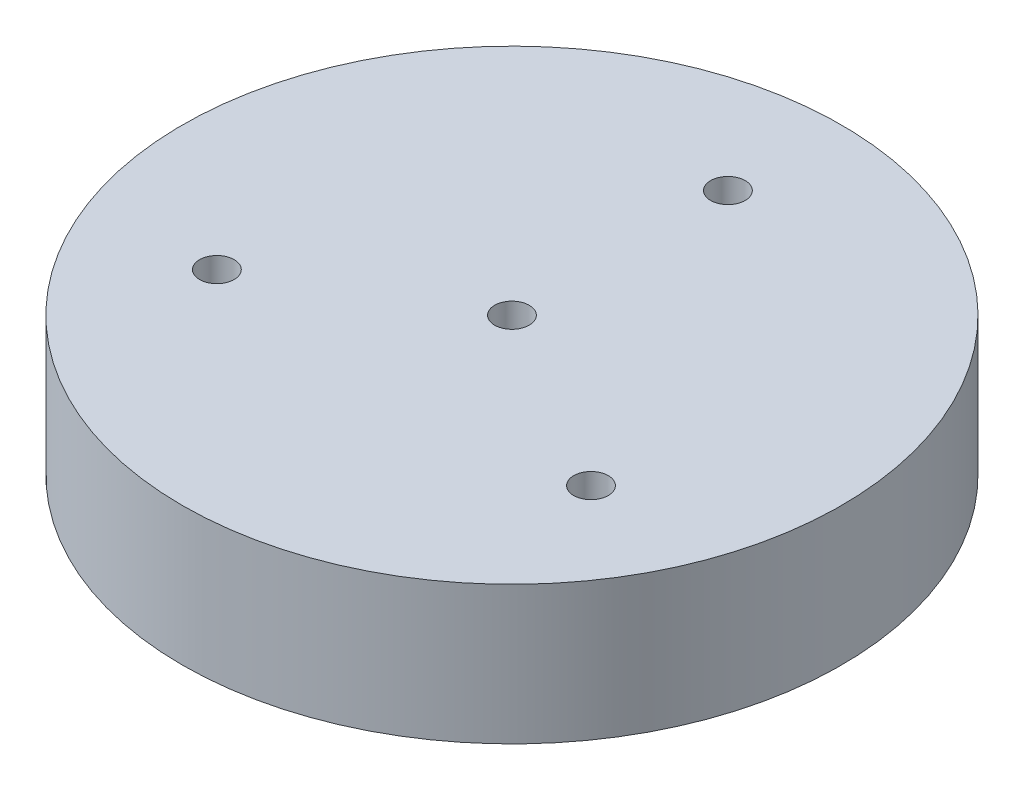
SolidWorks part; units mm, degrees
ref_plane "Ebene vorne" through (0, 0, 0) normal (0, 0, 1) x (1, 0, 0)
ref_plane "Ebene oben" through (0, 0, 0) normal (0, 1, 0) x (1, 0, 0)
ref_plane "Ebene rechts" through (0, 0, 0) normal (1, 0, 0) x (0, 0, -1)
sketch "Sketch1" plane through (0, 0, 0) normal (0, 1, 0) x (1, 0, 0)
  circle A0 centre (0, 0) radius 76.29
  dimension "D1" = 152.58
extrude "Boss-Extrude1" add sketch "Sketch1" along normal blind 32
sketch "Sketch2" plane through (0, 32, 0) normal (0, 1, 0) x (1, 0, 0)
  circle A0 centre (0, 50) radius 4
  dimension "D1" = 8
  dimension "D2" = 50
extrude "Cut-Extrude1" cut sketch "Sketch2" against normal through all contours A0
ref_axis "Axis1" through (0, 33.6, 0) along (0, -1, 0)
pattern_circular "CirPattern1" count 3 over 360 about axis through (0, 33.6, 0) along (0, -1, 0) of "Cut-Extrude1"
sketch "Sketch3" plane through (0, 32, 0) normal (0, 1, 0) x (1, 0, 0)
  circle A0 centre (0, 0) radius 4
  dimension "D1" = 8
extrude "Cut-Extrude2" cut sketch "Sketch3" against normal through all
